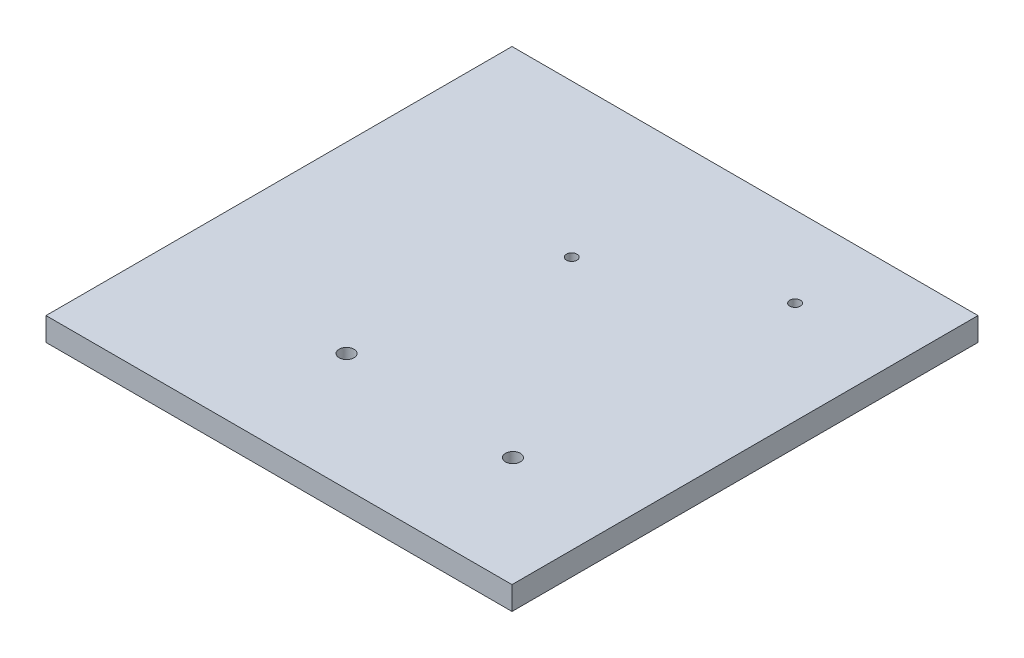
SolidWorks part; units mm, degrees
ref_plane "Front Plane" through (0, 0, 0) normal (0, 0, 1) x (1, 0, 0)
ref_plane "Top Plane" through (0, 0, 0) normal (0, 1, 0) x (1, 0, 0)
ref_plane "Right Plane" through (0, 0, 0) normal (1, 0, 0) x (0, 0, -1)
sketch "Sketch1" plane through (0, 0, 0) normal (0, 1, 0) x (1, 0, 0)
  line L0 (-66.0627, 0) -> (65.2437, 0) construction
  line L1 (-50, 50) -> (50, 50)
  line L2 (-50, 50) -> (-50, -50)
  line L3 (-50, -50) -> (50, -50)
  line L4 (50, 50) -> (50, -50)
  line L6 (30, -40) -> (-33.5, -40) construction
  line L7 (30, -40) -> (30, -15) construction
  line L8 (30, -15) -> (-33.5, -15) construction
  line L9 (-33.5, -40) -> (-33.5, -15) construction
  line L10 (-15.21, 35.09) -> (30, 35.09) construction
  line L11 (-15.21, 35.09) -> (-15.21, 15) construction
  line L12 (-15.21, 15) -> (30, 15) construction
  line L13 (30, 35.09) -> (30, 15) construction
  line L14 (-15.21, 35.09) -> (30, 15) construction
  line L15 (-15.21, 15) -> (30, 35.09) construction
  circle A0 centre (26.5, -26.3) radius 1.6
  circle A1 centre (-10.7, -24.8) radius 1.6
  circle A2 centre (28.07, 32.68) radius 1.13
  circle A3 centre (-4.44, 17.26) radius 1.13
  point P4 (50, 0)
  point P6 (0, 50)
  point P23 (7.395, 25.045)
  dimension "D5" = 3.2
  dimension "D10" = 3.2
  dimension "D17" = 2.26
  dimension "D18" = 2.26
  dimension "D1" = 100
  dimension "D2" = 100
  dimension "D3" = 15
  dimension "D4" = 20
  dimension "D6" = 3.5
  dimension "D7" = 13.7
  dimension "D8" = 63.5
  dimension "D9" = 25
  dimension "D11" = 40.7
  dimension "D12" = 15.2
  dimension "D13" = 45.21
  dimension "D14" = 20.09
  dimension "D15" = 15
  dimension "D16" = 20
  dimension "D19" = 15.42
  dimension "D20" = 17.68
  dimension "D21" = 32.51
  dimension "D22" = 1.93
extrude "Boss-Extrude1" add sketch "Sketch1" along normal blind 5
